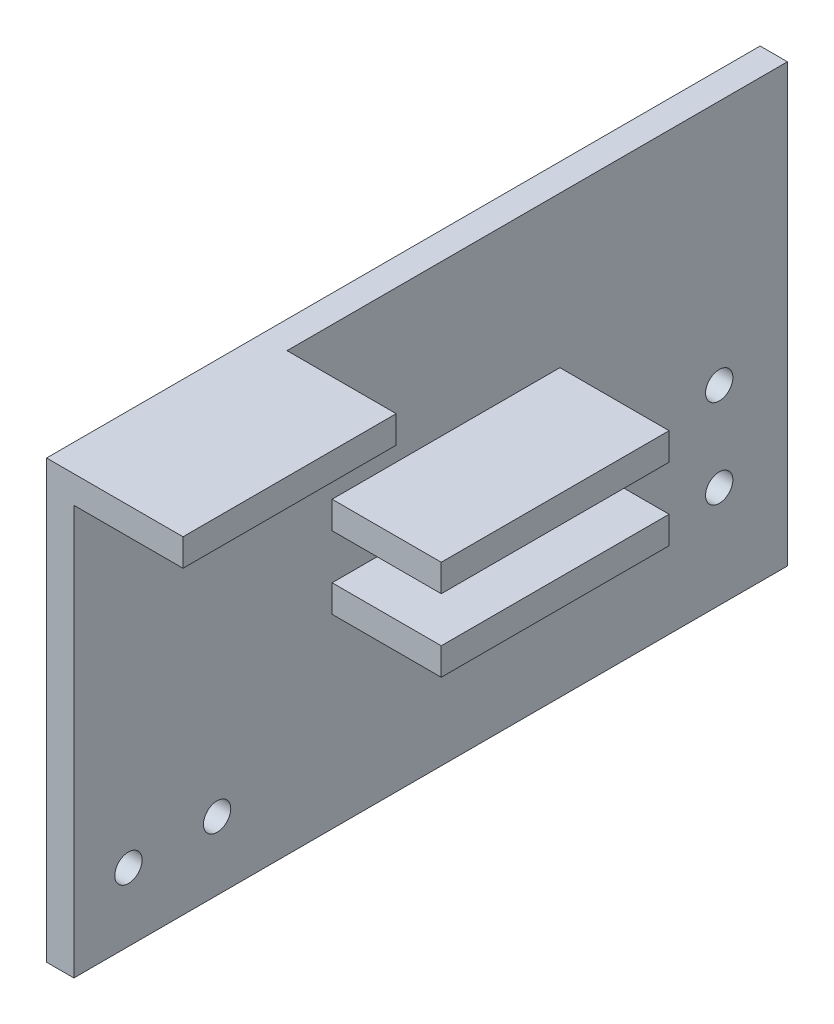
SolidWorks part; units mm, degrees
ref_plane "Front Plane" through (0, 0, 0) normal (0, 0, 1) x (1, 0, 0)
ref_plane "Top Plane" through (0, 0, 0) normal (0, 1, 0) x (1, 0, 0)
ref_plane "Right Plane" through (0, 0, 0) normal (1, 0, 0) x (0, 0, -1)
sketch "Sketch1" plane through (0, 0, 0) normal (1, 0, 0) x (0, 0, -1)
  line L0 (0, 14.732) -> (0, -17.275)
  line L1 (0, -17.275) -> (52.3, -17.275)
  line L2 (52.3, -17.275) -> (52.3, 14.732)
  line L3 (52.3, 14.732) -> (0, 14.732)
  line L4 (4, -12.275) -> (10.5, -12.275) construction
  line L5 (18.927, 3.651) -> (35.625, 3.651)
  line L6 (18.927, 3.651) -> (18.927, 1.651)
  line L7 (18.927, 1.651) -> (35.625, 1.651)
  line L8 (35.625, 3.651) -> (35.625, 1.651)
  line L9 (18.927, -1.651) -> (35.625, -1.651)
  line L10 (18.927, -1.651) -> (18.927, -3.651)
  line L11 (18.927, -3.651) -> (35.625, -3.651)
  line L12 (35.625, -1.651) -> (35.625, -3.651)
  line L13 (15.625, 14.732) -> (15.625, 3.675) construction
  line L14 (15.625, 3.675) -> (18.8, 3.675) construction
  line L15 (18.8, 3.675) -> (18.8, -8.875) construction
  line L16 (18.8, -8.875) -> (15.625, -8.875) construction
  line L17 (15.625, -8.875) -> (15.625, -17.275) construction
  line L18 (38.8, 1.651) -> (38.8, -1.651) construction
  line L19 (47.3, -9.8) -> (47.3, -3.3) construction
  line L24 (37.8, 0) -> (38.8, 0) construction
  line L26 (0, 14.732) -> (15.625, 14.732)
  line L27 (0, 14.732) -> (0, 12.732)
  line L28 (0, 12.732) -> (15.625, 12.732)
  line L29 (15.625, 14.732) -> (15.625, 12.732)
  circle A0 centre (4, -12.275) radius 1
  circle A1 centre (10.5, -12.275) radius 1
  circle A2 centre (47.3, -9.8) radius 1
  circle A3 centre (47.3, -3.3) radius 1
  point P19 (38.8, 0)
  point P24 (17.2125, 3.675)
  point P31 (37.8, 0)
  dimension "D1" = 2
  dimension "D9" = 3.4
  dimension "D2" = 6.5
  dimension "D3" = 3.302
  dimension "D4" = 2
  dimension "D5" = 5.125
  dimension "D6" = 4
  dimension "D7" = 5
  dimension "D8" = 3.175
  dimension "D10" = 12.55
  dimension "D11" = 3.675
  dimension "D12" = 0.127
  dimension "D13" = 2
  dimension "D14" = 9.057
  dimension "D15" = 20
  dimension "D16" = 6.35
  dimension "D17" = 9.5
  dimension "D18" = 3.3
  dimension "D19" = 1
  dimension "D20" = 5
extrude "Boss-Extrude1" add sketch "Sketch1" along normal blind 2 contours L28 L0 L1 L2 A3 A2 A1 A0 L5 L8 L7 L6 L9 L12 L11 L10 | L8 L5 L6 L7 | L12 L9 L10 L11 | L0 L28 L2 L3 region at (0, 13.732, -7.8125) region at (0, -1.5603, -26.4594) region at (0, 2.651, -27.276) region at (0, -2.651, -27.276)
extrude "Boss-Extrude2" add sketch "Sketch1<3>" along normal blind 10 contours L0 L28 L2 L3 | L8 L5 L6 L7 | L12 L9 L10 L11 region at (0, 13.732, -7.8125) region at (0, 2.651, -27.276) region at (0, -2.651, -27.276)
sketch "Sketch1<3>" plane through (0, 0, 0) normal (1, 0, 0) x (0, 0, -1) same geometry as "Sketch1"
